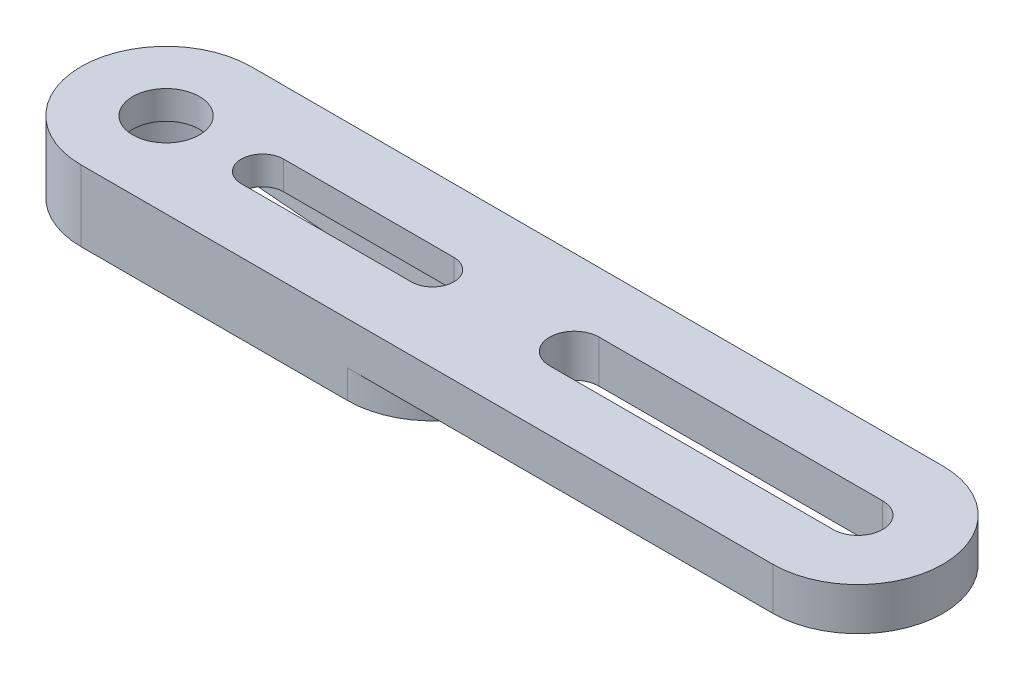
SolidWorks part; units mm, degrees
ref_plane "前视基准面" through (0, 0, 0) normal (0, 0, 1) x (1, 0, 0)
ref_plane "上视基准面" through (0, 0, 0) normal (0, 1, 0) x (1, 0, 0)
ref_plane "右视基准面" through (0, 0, 0) normal (1, 0, 0) x (0, 0, -1)
sketch "草图1" plane through (0, 0, 0) normal (0, 1, 0) x (1, 0, 0)
  line L0 (0, 0) -> (18.8, 0) construction
  line L1 (0.3271, 4.0869) -> (19.0074, 2.5917)
  line L2 (19.0074, -2.5917) -> (0.3271, -4.0869)
  line L3 (0, 0) -> (-4.1, 0) construction
  line L4 (18.8, 0) -> (21.4, 0) construction
  line L5 (18.8, 6) -> (0, 6)
  line L6 (0, -6) -> (18.8, -6)
  circle A0 centre (0, 0) radius 4.1
  circle A1 centre (18.8, 0) radius 2.6
  circle A2 centre (0, 0) radius 6
  circle A3 centre (18.8, 0) radius 6
  circle A4 centre (0, 0) radius 2.35
  dimension "D1" = 8.2
  dimension "D2" = 5.2
  dimension "D3" = 25.5
  dimension "D4" = 12
  dimension "D5" = 12
  dimension "D6" = 4.7
extrude "凸台-拉伸1" add sketch "草图1" against normal blind 3 contours L5 | A2 L2 A0 L1 | A3 L5 A2 L1 | A3 L1 A1 L2 | A3 L2 A2 L6 region at (-4.2607, 0, 0) region at (9.5507, 0, -4.821) region at (15.8933, 0, -5.0606) region at (9.5507, 0, 4.821)
extrude "凸台-拉伸2" add sketch "草图1<4>" along normal blind 2 contours A0 | L2 A2 L1 A0 | A3 L1 A2 L2 | L1 A3 L2 A1 | A1 | A3 L1 A1 L2 | A3 L5 A2 L1 | A3 L2 A2 L6 | A2 L2 A0 L1 region at (-4.2607, 0, 0) region at (4.3234, 0, 0) region at (2.9274, 0, -2.7024) region at (9.5507, 0, -4.821) region at (9.2138, 0, 0) region at (15.8933, 0, -5.0606) region at (14.9575, 0, 0) region at (9.5507, 0, 4.821) region at (18.8, 0, 0)
sketch "草图1<4>" plane through (0, 0, 0) normal (0, 1, 0) x (1, 0, 0) same geometry as "草图1"
sketch "草图2" plane through (0, 2, 0) normal (0, 1, 0) x (1, 0, 0)
  line L0 (0, 0) -> (107.5918, 0) construction
  line L1 (48.8, 1.75) -> (28.8, 1.75)
  line L2 (0, -6) -> (18.8, -6)
  line L3 (18.8, 6) -> (0, 6)
  line L4 (0, -6) -> (18.8, -6)
  line L5 (18.8, 6) -> (0, 6)
  line L6 (48.8, -1.75) -> (28.8, -1.75)
  line L7 (48.8, 6) -> (18.8, 6)
  line L8 (48.8, -6) -> (18.8, -6)
  line L9 (18.8, 1.5) -> (6.8, 1.5)
  line L10 (18.8, -1.5) -> (6.8, -1.5)
  circle A0 centre (28.8, 0) radius 1.75
  circle A1 centre (48.8, 0) radius 1.75
  arc A2 (18.8, -6) -> (18.8, 6) centre (18.8, 0) ccw
  arc A3 (0, 6) -> (0, -6) centre (0, 0) ccw
  arc A4 (18.8, -6) -> (18.8, 6) centre (18.8, 0) ccw
  arc A5 (0, 6) -> (0, -6) centre (0, 0) ccw
  circle A6 centre (48.8, 0) radius 6
  circle A8 centre (18.8, 0) radius 1.5
  circle A9 centre (6.8, 0) radius 1.5
  point P25 (7.7651, 1.5)
  point P26 (7.7651, -1.5)
  arc M6 (18.8, -6) -> (18.8, 6) centre (18.8, 0) ccw
  dimension "D2" = 3.5
  dimension "D3" = 3.5
  dimension "D5" = 12
  dimension "D6" = 30
  dimension "D7" = 3
  dimension "D8" = 3
  dimension "D4" = 20
  dimension "D9" = 12
  dimension "D1" = 0
extrude "凸台-拉伸3" add sketch "草图2" against normal blind 3 contours L0 L8 A6 L6 A0 M6 | A4 L0 A0 L1 A6 L7 | A1 L0 A6 L1 | L0 A1 L6 A6 region at (49.4581, 2, -3.0421) region at (49.4581, 2, 3.0421) region at (33.4208, 2, -3.8651) region at (33.4208, 2, 3.8651)
extrude "切除-拉伸1" cut sketch "草图2<3>" against normal blind 10 contours A9 L0 | L0 A9 | A9 L0 A8 L9 | L0 A9 L10 A8 | A8 L0 | L0 A8 region at (18.8, 2, 0.6366) region at (18.8, 2, -0.6366) region at (12.8, 2, 0.7777) region at (12.8, 2, -0.7777) region at (6.8, 2, 0.6366) region at (6.8, 2, -0.6366)
sketch "草图2<3>" plane through (0, 2, 0) normal (0, 1, 0) x (1, 0, 0) same geometry as "草图2"
